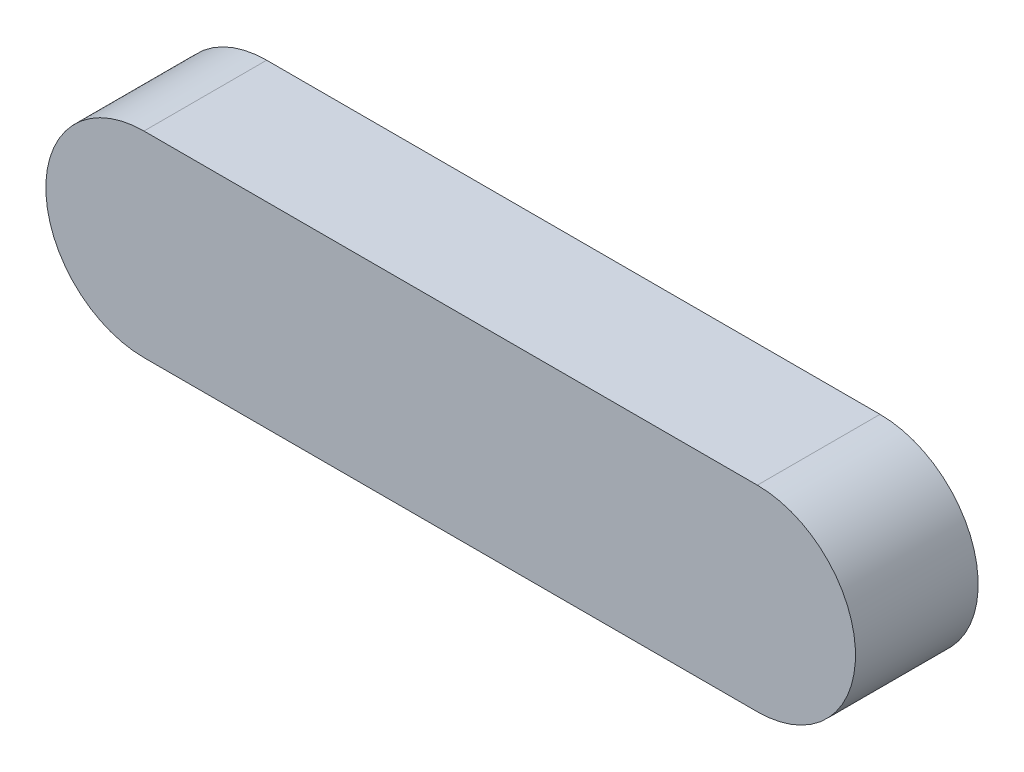
SolidWorks part; units mm, degrees
ref_plane "정면" through (0, 0, 0) normal (0, 0, 1) x (1, 0, 0)
ref_plane "윗면" through (0, 0, 0) normal (0, 1, 0) x (1, 0, 0)
ref_plane "우측면" through (0, 0, 0) normal (1, 0, 0) x (0, 0, -1)
sketch "스케치1" plane through (0, 0, 0) normal (0, 0, 1) x (1, 0, 0)
  line L0 (0, 0) -> (-250, 0) construction
  line L1 (0, -40) -> (-250, -40)
  line L2 (0, 40) -> (-250, 40)
  arc A0 (0, -40) -> (0, 40) centre (0, 0) ccw
  arc A1 (-250, 40) -> (-250, -40) centre (-250, 0) ccw
  circle A2 centre (-250, 0) radius 30
  circle A3 centre (0, 0) radius 30
  circle A4 centre (-187.5, 0) radius 30
  circle A5 centre (-62.5, 0) radius 30
  circle A6 centre (-125, 0) radius 30
  point P3 (-125, 0)
  point P18 (0, 0)
  dimension "D2" = 40
  dimension "D3" = 60
  dimension "D4" = 60
  dimension "D5" = 60
  dimension "D6" = 60
  dimension "D9" = 60
  dimension "D1" = 250
  dimension "D7" = 62.5
  dimension "D8" = 62.5
extrude "보스-돌출1" add sketch "스케치1" along normal blind 50 contours A2 | A4 L0 | L0 A4 | L2 A1 L1 A0 A3 A5 A6 A4 A2 | L0 A6 | A6 L0 | L0 A5 | A5 L0 | A3 region at (-279.1515, 0, 0) region at (-187.5, -12.7324, 0) region at (-187.5, 12.7324, 0) region at (-125, -12.7324, 0) region at (-125, 12.7324, 0) region at (-62.5, -12.7324, 0) region at (-62.5, 12.7324, 0) region at (-125, -36.6044, 0)
extrude "컷-돌출1" cut sketch "스케치1<3>" along normal blind 40 contours A3 | L0 A5 | A5 L0 | L0 A6 | A6 L0 | L0 A4 | A4 L0 | A2 region at (-279.1515, 0, 0) region at (-187.5, -12.7324, 0) region at (-187.5, 12.7324, 0) region at (-125, -12.7324, 0) region at (-125, 12.7324, 0) region at (-62.5, -12.7324, 0) region at (-62.5, 12.7324, 0) region at (0, 29.1515, 0)
sketch "스케치1<3>" plane through (0, 0, 0) normal (0, 0, 1) x (1, 0, 0) same geometry as "스케치1"
